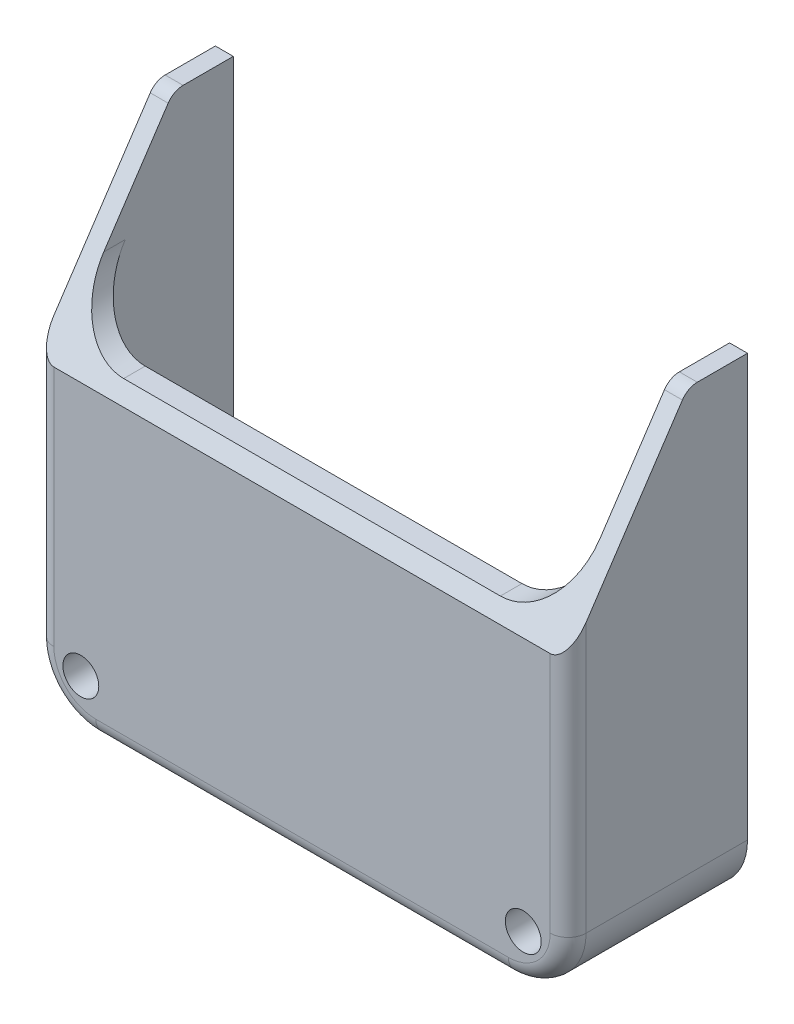
SolidWorks part; units mm, degrees
material "ABS"
ref_plane "Plano frontal" through (0, 0, 0) normal (0, 0, 1) x (1, 0, 0)
ref_plane "Plano superior" through (0, 0, 0) normal (0, 1, 0) x (1, 0, 0)
ref_plane "Plano direito" through (0, 0, 0) normal (1, 0, 0) x (0, 0, -1)
sketch "Esboço1" plane through (0, 0, 0) normal (0, 0, 1) x (1, 0, 0)
  line L1 (-44.5, -35.5) -> (44.5, -35.5)
  line L2 (-44.5, -35.5) -> (-44.5, 45)
  line L3 (-44.5, 45) -> (44.5, 45)
  line L4 (44.5, -35.5) -> (44.5, 45)
  point P0 (0, 0)
  dimension "D1" = 89
  dimension "D2" = 45
  dimension "D3" = 35.5
extrude "Ressalto-extrusão1" add sketch "Esboço1" along normal blind 30
fillet "Filete1" radius 10 2 edges at (-44.5, -35.5, 15) (44.5, -35.5, 15)
chamfer "Chanfro1" distance 20 distance2 30 1 edges at (0, 45, 30) first distance on face at (0, 45, 15)
fillet "Filete2" radius 3 5 edges at (44.5, -5.25, 30) (41.5711, -32.5711, 30) (0, -35.5, 30) (-41.5711, -32.5711, 30) (-44.5, -5.25, 30)
shell "Casca1" thickness 3 removed face at (0, -6.0237, 0)
sketch "Esboço2" plane through (0, 0, 30) normal (0, 0, 1) x (1, 0, 0)
  line L1 (-41.5, 45) -> (41.5, 45)
  line L2 (-41.5, 45) -> (-41.5, 17.5)
  line L3 (-41.5, 17.5) -> (41.5, 17.5)
  line L4 (41.5, 45) -> (41.5, 17.5)
  line L5 (44.5, 19.5) -> (44.5, -25.5) construction
  line L6 (-44.5, -25.5) -> (-44.5, 19.5) construction
  line L7 (41.5, 45) -> (-41.5, 45) construction
  dimension "D1" = 17.5
  dimension "D2" = 0
  dimension "D3" = 3
  dimension "D4" = 3
extrude "Corte-extrusão1" cut sketch "Esboço2" against normal through all
fillet "Filete3" radius 10 2 edges at (41.5, 17.5, 26.5306) (-41.5, 17.5, 26.5306)
sketch "Esboço3" plane through (0, 0, 27) normal (0, 0, -1) x (-1, 0, 0)
  line L0 (0, 0) -> (0, -35.5) construction
  line L1 (34.5, -35.5) -> (-34.5, -35.5) construction
  circle A0 centre (-37, -27.5) radius 3
  circle A1 centre (37, -27.5) radius 3
  dimension "D1" = 37
  dimension "D2" = 27.5
  dimension "D3" = 6
extrude "Ressalto-extrusão2" add sketch "Esboço3" along normal blind 14
sketch "Esboço4" plane through (0, 0, 13) normal (0, 0, -1) x (-1, 0, 0)
  line L0 (0, 17.5) -> (0, -35.5) construction
  line L1 (-31.5, 17.5) -> (31.5, 17.5) construction
  line L2 (34.5, -35.5) -> (-34.5, -35.5) construction
  circle A0 centre (-37, -27.5) radius 1.75
  circle A1 centre (37, -27.5) radius 1.75
  dimension "D1" = 3.5
extrude "Corte-extrusão2" cut sketch "Esboço4" against normal through all
sketch "Esboço6" plane through (0, 0, 27) normal (0, 0, -1) x (-1, 0, 0)
  line L0 (-37, -22.5) -> (-41.5, -22.5)
  line L1 (-41.5, -25.5) -> (-41.5, 45) construction
  line L2 (-41.5, -22.5) -> (-41.5, -32.5)
  line L3 (-41.5, -32.5) -> (-37, -32.5)
  line L4 (0, 0) -> (0, -35.5) construction
  line L5 (34.5, -35.5) -> (-34.5, -35.5) construction
  line L6 (41.5, -32.5) -> (37, -32.5)
  line L7 (41.5, -22.5) -> (41.5, -32.5)
  line L8 (37, -22.5) -> (41.5, -22.5)
  circle A0 centre (-37, -27.5) radius 1.75
  arc A1 (-37, -32.5) -> (-37, -22.5) centre (-37, -27.5) ccw
  arc A2 (37, -32.5) -> (37, -22.5) centre (37, -27.5) cw
  circle A3 centre (37, -27.5) radius 1.75
  dimension "D1" = 10
extrude "Ressalto-extrusão3" add sketch "Esboço6" along normal blind 10
sketch "Esboço8" plane through (0, 0, 30) normal (0, 0, 1) x (1, 0, 0)
  line L0 (0, 0) -> (0, -35.5) construction
  line L1 (34.5, -35.5) -> (-34.5, -35.5) construction
  circle A0 centre (-37, -27.5) radius 3
  circle A1 centre (37, -27.5) radius 3
  dimension "D1" = 6
extrude "Corte-extrusão3" cut sketch "Esboço8" against normal offset from surface (11 mm away) 2 up to face at (-34, -27.5, 17)
fillet "Filete4" radius 3 2 edges at (43, 45, 10) (-43, 45, 10)
chamfer "Chanfro2" distance 1 distance2 4 1 edges at (34, -27.5, 17) first distance on face at (34, -27.5, 17)
chamfer "Chanfro3" distance 4 distance2 1 1 edges at (-34, -27.5, 17) first distance on face at (-34, -27.5, 13)
fillet "Filete5" radius 3 5 edges at (35.1813, -32.4668, 27) (-35.1813, -32.4668, 27) (-41.5, -4.2042, 27) (0, -32.5, 27) (41.5, -4.2042, 27)
